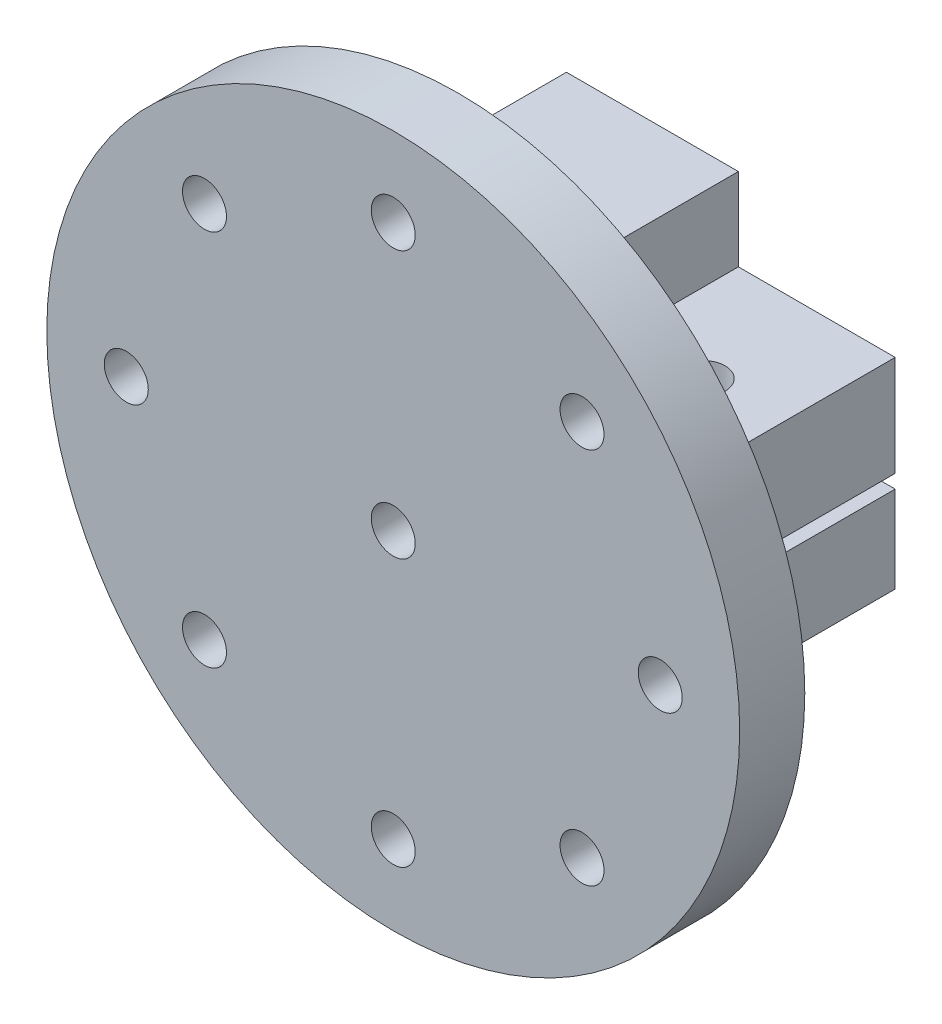
SolidWorks part; units mm, degrees
ref_plane "Front Plane" through (0, 0, 0) normal (0, 0, 1) x (1, 0, 0)
ref_plane "Top Plane" through (0, 0, 0) normal (0, 1, 0) x (1, 0, 0)
ref_plane "Right Plane" through (0, 0, 0) normal (1, 0, 0) x (0, 0, -1)
sketch "草图1" plane through (0, 0, 0) normal (0, 0, 1) x (1, 0, 0)
  line L0 (0, 0) -> (6, 0)
  line L1 (6, 0) -> (7, 0)
  line L3 (0, 0) -> (0, -2)
  line L5 (7, -2) -> (7, 0)
  line L6 (0, 0) -> (0, 6)
  line L8 (0, 2) -> (0, 0)
  line L9 (0, 0) -> (7, 0)
  line L10 (7, 2) -> (7, 0)
  line L11 (0, 0) -> (-6, 0)
  line L12 (-6, 6) -> (6, -6) construction
  line L13 (6, 6) -> (-6, -6) construction
  line L14 (-6, 6) -> (-7.4142, 7.4142) construction
  line L16 (-6, 6) -> (-6, -6)
  line L17 (-6, 6) -> (6, 6)
  line L18 (-6, 6) -> (-6, -6)
  line L19 (-6, -6) -> (6, -6)
  line L20 (6, 6) -> (6, -6)
  line L23 (-7.4142, 7.4142) -> (-7.4142, -7.4142) construction
  line L24 (0, 2) -> (6, 2)
  line L25 (-7.4142, 7.4142) -> (22.5858, 7.4142)
  line L26 (-7.4142, 7.4142) -> (-7.4142, -7.4142)
  line L27 (-7.4142, -7.4142) -> (22.5858, -7.4142)
  line L28 (22.5858, 7.4142) -> (22.5858, -7.4142)
  line L29 (6, 2) -> (6, -2)
  line L30 (6, -2) -> (0, -2)
  line L32 (6, 2) -> (7, 2)
  line L33 (6, 2) -> (6, -2)
  line L34 (6, -2) -> (7, -2)
  line L35 (7, 2) -> (7, -2)
  line L36 (0, 2) -> (6, 2)
  line L37 (0, 2) -> (0, -2)
  line L38 (0, -2) -> (6, -2)
  line L39 (6, 2) -> (6, -2)
  line L41 (6, 3) -> (6, -3)
  line L42 (6, 3) -> (18, 3)
  line L43 (6, 3) -> (6, -3)
  line L44 (6, -3) -> (18, -3)
  line L45 (18, 3) -> (18, -3)
  line L47 (7, 2) -> (7, -2)
  line L49 (18, 2) -> (18, -2)
  line L50 (18, -1) -> (7, -1)
  line L51 (18, -1) -> (18, 1)
  line L52 (18, 1) -> (7, 1)
  line L53 (7, -1) -> (7, 1)
  line L54 (18, 3) -> (20.8501, 3)
  line L55 (18, 3) -> (18, 1)
  line L56 (18, 1) -> (20.8501, 1)
  line L57 (20.8501, 3) -> (20.8501, 1)
  line L62 (18, -1) -> (20.8501, -1)
  line L63 (18, -1) -> (18, -3)
  line L64 (18, -3) -> (20.8501, -3)
  line L65 (20.8501, -1) -> (20.8501, -3)
  line L66 (7, 2) -> (7.7, 2)
  line L67 (7, 2) -> (7, 1)
  line L68 (7, 1) -> (7.7, 1)
  line L69 (7.7, 2) -> (7.7, 1)
  line L70 (7, -2) -> (7.7, -2)
  line L71 (7, -2) -> (7, -1)
  line L72 (7, -1) -> (7.7, -1)
  line L73 (7.7, -2) -> (7.7, -1)
  circle A0 centre (0, 0) radius 6
  circle A2 centre (0, 0) radius 10.4853
  point P20 (6, 2)
  point P21 (6, -2)
  point P22 (6, 3)
  point P25 (6, -3)
  point P30 (10.2928, 2)
  point P31 (10.2928, -2)
  point P32 (18, 1)
  point P33 (18, -1)
  point P34 (18, 1)
  dimension "D1" = 12
  dimension "D2" = 6
  dimension "D3" = 2
  dimension "D4" = 12
  dimension "D5" = 12
  dimension "D6" = 2
  dimension "D7" = 30
  dimension "D8" = 14.8284
  dimension "D9" = 6
extrude "凸台-拉伸2" add sketch "草图1" along normal blind 33 contours L25 L28 L27 L26
extrude "切除-拉伸9" cut sketch "草图1<11>" along normal blind 46 contours L11 A0 L3 region at (-0.7742, -2.9557, 0)
sketch "草图1<11>" plane through (0, 0, 0) normal (0, 0, 1) x (1, 0, 0) same geometry as "草图1"
extrude "切除-拉伸10" cut sketch "草图1<12>" along normal blind 30 contours L6 A0 L11 region at (-2.5465, 2.5465, 0)
sketch "草图1<12>" plane through (0, 0, 0) normal (0, 0, 1) x (1, 0, 0) same geometry as "草图1"
extrude "切除-拉伸12" cut sketch "草图1<14>" along normal blind 40 contours A0 L0 L3 region at (2.9444, -0.9903, 0)
sketch "草图1<14>" plane through (0, 0, 0) normal (0, 0, 1) x (1, 0, 0) same geometry as "草图1"
extrude "切除-拉伸13" cut sketch "草图1<15>" along normal blind 46 contours A0 L6 region at (2.2626, 3.6569, 0)
sketch "草图1<15>" plane through (0, 0, 0) normal (0, 0, 1) x (1, 0, 0) same geometry as "草图1"
extrude "切除-拉伸18" cut sketch "草图1<20>" along normal blind 285 contours A2 L49 L27 L28 L25 region at (9.1874, 5.4796, 0)
sketch "草图1<20>" plane through (0, 0, 0) normal (0, 0, 1) x (1, 0, 0) same geometry as "草图1"
sketch "草图12" plane through (0, 0, 33) normal (0, 0, 1) x (1, 0, 0)
  line L0 (0, 0) -> (0, 50)
  line L5 (0, 0) -> (-35.3553, 35.3553)
  line L6 (-35.3553, 35.3553) -> (35.3553, -35.3553)
  line L7 (35.3553, 0) -> (41.7053, 0)
  line L8 (-35.3553, 35.3553) -> (35.3553, 35.3553)
  line L9 (-35.3553, 35.3553) -> (-35.3553, -35.3553)
  line L10 (-35.3553, -35.3553) -> (35.3553, -35.3553)
  line L11 (35.3553, 35.3553) -> (35.3553, -35.3553)
  circle A0 centre (0, 0) radius 50
  circle A9 centre (38.5303, 0) radius 3.175
  circle A10 centre (27.2451, -27.2451) radius 3.175
  circle A11 centre (0, -38.5303) radius 3.175
  circle A12 centre (-27.2451, -27.2451) radius 3.175
  circle A13 centre (-38.5303, 0) radius 3.175
  circle A14 centre (-27.2451, 27.2451) radius 3.175
  circle A15 centre (0, 38.5303) radius 3.175
  circle A16 centre (27.2451, 27.2451) radius 3.175
  point P11 (-25, 25)
  point P12 (-25, -25)
  point P13 (24.6474, -24.6474)
  point P31 (0, 0)
  point P33 (0, 0)
  dimension "D1" = 6.35
  dimension "D2" = 8
extrude "凸台-拉伸7" add sketch "草图12" along normal blind 9.398 contours A0
extrude "切除-拉伸27" cut sketch "草图12<5>" along normal blind 63 contours A16 | A14 | A13 | A12 | A11 | A10 | A9 | A15 region at (27.2451, 27.2451, 33)
sketch "草图12<5>" plane through (0, 0, 33) normal (0, 0, 1) x (1, 0, 0) same geometry as "草图12"
sketch "草图20" plane through (0, 0, 0) normal (0, 0, -1) x (-1, 0, 0)
  circle A0 centre (0, 0) radius 3.175
  circle A1 centre (0, 0) radius 6
  dimension "D1" = 6.35
  dimension "D2" = 12
extrude "凸台-拉伸9" add sketch "草图20" against normal blind 3
extrude "切除-拉伸29" cut sketch "草图1<26>" along normal blind 31 contours A2 L50 L49 L52 | L50 A2 L52 L47 region at (8.7347, 0, 0) region at (14.2347, 0, 0)
sketch "草图1<26>" plane through (0, 0, 0) normal (0, 0, 1) x (1, 0, 0) same geometry as "草图1"
extrude "切除-拉伸30" cut sketch "草图1<27>" along normal blind 33 contours L0 A0 L24 L6 | A2 L50 L49 L52 | L50 A2 L52 L47 region at (2.9444, 0.9903, 0) region at (8.7347, 0, 0) region at (14.2347, 0, 0)
sketch "草图1<27>" plane through (0, 0, 0) normal (0, 0, 1) x (1, 0, 0) same geometry as "草图1"
extrude "切除-拉伸31" cut sketch "草图1<28>" along normal blind 33 contours L6 A0 L11 | L38 A0 L0 L3 | A0 L30 L20 | A0 L20 L36 | L32 L20 L1 L47 L10 | L20 L34 L5 L47 L1 region at (2.9444, -0.9903, 0) region at (-2.5465, 2.5465, 0) region at (6.5, 1, 0) region at (5.8976, 1.5029, 0) region at (6.5, -1, 0) region at (5.8976, -1.5029, 0)
sketch "草图1<28>" plane through (0, 0, 0) normal (0, 0, 1) x (1, 0, 0) same geometry as "草图1"
extrude "切除-拉伸32" cut sketch "草图1<29>" along normal blind 33 contours L24 A0 L6 | L11 A0 L38 L3 region at (-0.7742, -2.9557, 0) region at (2.2626, 3.6569, 0)
sketch "草图1<29>" plane through (0, 0, 0) normal (0, 0, 1) x (1, 0, 0) same geometry as "草图1"
sketch "草图21" plane through (0, 0, 0) normal (0, 0, -1) x (-1, 0, 0)
  circle A0 centre (0, 0) radius 3.175
  circle A1 centre (0, 0) radius 6
  dimension "D1" = 6.35
  dimension "D2" = 12
extrude "凸台-拉伸11" add sketch "草图21" against normal blind 34
extrude "切除-拉伸34" cut sketch "草图21<5>" against normal blind 31
sketch "草图21<5>" plane through (0, 0, 0) normal (0, 0, -1) x (-1, 0, 0) same geometry as "草图21"
sketch "草图22" plane through (0, 0, 33) normal (0, 0, -1) x (-1, 0, 0)
  circle A0 centre (0, 0) radius 3.175
  dimension "D1" = 6.35
extrude "切除-拉伸35" cut sketch "草图22" against normal blind 31
sketch "草图24" plane through (0, 0, 0) normal (0, 0, -1) x (-1, 0, 0)
  line L1 (-7.4142, 7.4142) -> (17.4009, 7.4142)
  line L2 (-7.4142, 7.4142) -> (-7.4142, 27.4142)
  line L3 (-7.4142, 27.4142) -> (17.4009, 27.4142)
  line L4 (17.4009, 7.4142) -> (17.4009, 27.4142)
  line L5 (7.4142, 7.4142) -> (17.4009, 7.4142)
  line L6 (7.4142, 7.4142) -> (7.4142, -6.6479)
  line L7 (7.4142, -6.6479) -> (17.4009, -6.6479)
  line L8 (17.4009, 7.4142) -> (17.4009, -6.6479)
  line L9 (17.4009, -6.6479) -> (-7.5991, -6.6479)
  line L10 (17.4009, -6.6479) -> (17.4009, -26.6479)
  line L11 (17.4009, -26.6479) -> (-7.5991, -26.6479)
  line L12 (-7.5991, -6.6479) -> (-7.5991, -26.6479)
  line M22 (7.4142, -7.4142) -> (7.4142, 7.4142)
  line M23 (7.4142, 7.4142) -> (-7.4142, 7.4142)
  dimension "D1" = 20
  dimension "D2" = 20
  dimension "D3" = 25
extrude "凸台-拉伸12" add sketch "草图24" against normal blind 33 contours L10 L11 L12 L9
extrude "凸台-拉伸13" add sketch "草图24<3>" against normal blind 34 contours L8 L1 L7 M22 | L1 L4 L3 L2 M23 region at (-4.9934, 17.4142, 0) region at (-12.4076, 0.3832, 0)
sketch "草图24<3>" plane through (0, 0, 0) normal (0, 0, -1) x (-1, 0, 0) same geometry as "草图24"
sketch "草图25" plane through (0, 0, 0) normal (0, 0, -1) x (-1, 0, 0)
  line L0 (-20.8501, 3) -> (-20.8501, 1)
  line L1 (-10.0469, -3) -> (-30.0469, -3)
  line L2 (-10.0469, -3) -> (-10.0469, -0.9612)
  line L3 (-10.0469, -0.9612) -> (-30.0469, -0.9612)
  line L4 (-30.0469, -3) -> (-30.0469, -0.9612)
  line L5 (-10.0469, 3) -> (-30.0469, 3)
  line L6 (-10.0469, 3) -> (-10.0469, 1)
  line L7 (-10.0469, 1) -> (-30.0469, 1)
  line L8 (-30.0469, 3) -> (-30.0469, 1)
  line L9 (-20.8501, 1) -> (-20.8501, -3)
  line L10 (-20.8501, -3) -> (-20.8501, -1)
  line M4 (-20.8501, 3) -> (-20.8501, 1)
  line M12 (-20.8501, -1) -> (-20.8501, -3)
  dimension "D1" = 20
  dimension "D2" = 20
extrude "凸台-拉伸14" add sketch "草图25" against normal blind 33 contours L9 L3 L4 L1 M12 | L5 L8 L7 M4 region at (25.4485, -1.9806, 0) region at (25.4485, 2, 0)
sketch "草图26" plane through (0, 0, 0) normal (0, 0, -1) x (-1, 0, 0)
  line L2 (-30.0469, -0.9612) -> (-7.5991, -0.9612)
  line L3 (-30.0469, -0.9612) -> (-30.0469, -15.9612)
  line L6 (-7.4142, 27.4142) -> (-7.4142, 7.4142) construction
  line L7 (-30.0469, 3) -> (-7.4142, 3)
  line L8 (-30.0469, 3) -> (-30.0469, 18)
  line L9 (-30.0469, 18) -> (-7.4142, 18)
  line L10 (-7.4142, 3) -> (-7.4142, 18)
  line L11 (-30.0469, -15.9612) -> (-7.5991, -15.9612)
  line L12 (-7.5991, -26.6479) -> (-7.5991, -7.2246) construction
  line M5 (-7.4142, 27.4142) -> (-7.4142, 7.4142)
  arc M6 (-7.4142, 7.4142) -> (-10.0469, 3) centre (0, 0) ccw
  line M7 (-10.0469, 3) -> (-30.0469, 3)
  line M19 (-30.0469, -3) -> (-10.0469, -3)
  arc M20 (-10.0469, -3) -> (-7.5991, -7.2246) centre (0, 0) ccw
  line M21 (-7.5991, -7.2246) -> (-7.5991, -26.6479)
  dimension "D1" = 15
  dimension "D2" = 15
extrude "凸台-拉伸15" add sketch "草图26" against normal blind 36 contours L9 L8 M7 M6 M5 | L3 L11 M21 M20 M19 region at (19.0446, -9.5869, 0) region at (18.9456, 10.6226, 0)
sketch "草图27" plane through (0, -15.9612, 0) normal (0, -1, 0) x (1, 0, 0)
  line L0 (30.0469, 33) -> (7.5991, 0) construction
  line L1 (7.5991, 0) -> (30.0469, 0)
  line L2 (30.0469, 0) -> (7.5991, 33) construction
  circle A0 centre (18.823, 16.5) radius 3.175
  point P4 (18.823, 16.5)
  dimension "D1" = 6.35
sketch "草图28" plane through (0, 0, 0) normal (0, 0, -1) x (-1, 0, 0)
  line L0 (-30.0469, 18) -> (-30.0469, 1) construction
  line L1 (-7.4142, 18) -> (-30.0469, 18)
  line L2 (-7.4142, 18) -> (-7.4142, 15.5)
  line L3 (-7.4142, 15.5) -> (-30.0469, 15.5)
  line L4 (-30.0469, 18) -> (-30.0469, 15.5)
  line L5 (-30.0469, -15.9612) -> (-30.0469, -0.9612) construction
  line L6 (-7.5991, -15.9612) -> (-30.0469, -15.9612)
  line L7 (-7.5991, -15.9612) -> (-7.5991, -13.4612)
  line L8 (-7.5991, -13.4612) -> (-30.0469, -13.4612)
  line L9 (-30.0469, -15.9612) -> (-30.0469, -13.4612)
  dimension "D1" = 2.5
  dimension "D2" = 2.5
extrude "切除-拉伸43" cut sketch "草图28" against normal blind 33
extrude "切除-拉伸45" cut sketch "草图1<32>" along normal blind 33 contours L69 L66 L10 L52 | L70 L73 L50 L5 region at (7.35, -1.5, 0) region at (7.35, 1.5, 0)
sketch "草图1<32>" plane through (0, 0, 0) normal (0, 0, 1) x (1, 0, 0) same geometry as "草图1"
sketch "草图29" plane through (0, 0, 0) normal (0, 0, -1) x (-1, 0, 0)
  line L0 (17.4009, 27.4142) -> (17.4009, -26.6479) construction
  line L1 (-30.0469, 15.5) -> (17.4009, 15.5)
  line L2 (-30.0469, 15.5) -> (-30.0469, -13.4399)
  line L3 (-30.0469, -13.4399) -> (17.4009, -13.4399)
  line L4 (17.4009, 15.5) -> (17.4009, -13.4399)
  line L6 (-7.4142, 27.4142) -> (17.4009, 27.4142)
  line L7 (-7.4142, 27.4142) -> (-7.4142, 15.5)
  line L8 (-7.4142, 15.5) -> (17.4009, 15.5)
  line L9 (17.4009, 27.4142) -> (17.4009, 15.5)
  line L10 (-7.5991, -13.4612) -> (17.4009, -13.4612)
  line L11 (-7.5991, -13.4612) -> (-7.5991, -26.6479)
  line L12 (-7.5991, -26.6479) -> (17.4009, -26.6479)
  line L13 (17.4009, -13.4612) -> (17.4009, -26.6479)
extrude "切除-拉伸46" cut sketch "草图27" against normal blind 70 contours A0
sketch "草图31" plane through (0, 0, 42.398) normal (0, 0, 1) x (1, 0, 0)
  circle A0 centre (0, 0) radius 50
